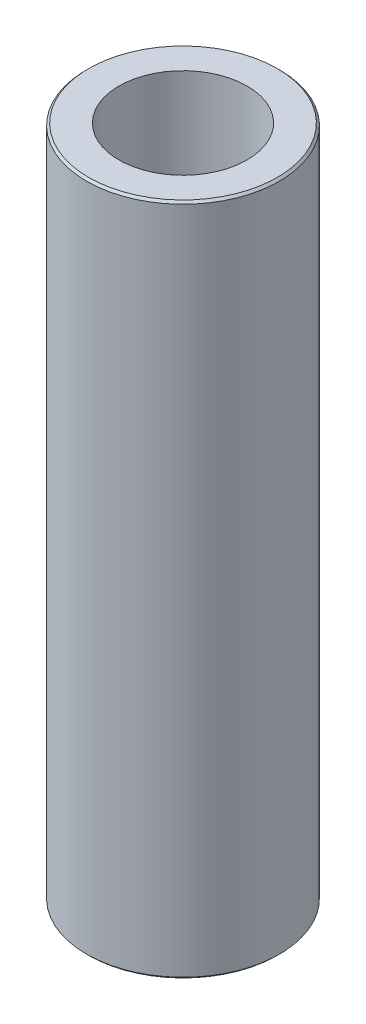
SolidWorks part; units mm, degrees
ref_plane "Front Plane" through (0, 0, 0) normal (0, 0, 1) x (1, 0, 0)
ref_plane "Top Plane" through (0, 0, 0) normal (0, 1, 0) x (1, 0, 0)
ref_plane "Right Plane" through (0, 0, 0) normal (1, 0, 0) x (0, 0, -1)
sketch "Sketch1" plane through (0, 0, 0) normal (0, 1, 0) x (1, 0, 0)
  circle A0 centre (0, 0) radius 45
  dimension "SHAFT_OD" = 90
extrude "Boss-Extrude1" add sketch "Sketch1" along normal blind 314.2264
sketch "Sketch2" plane through (0, 0, 0) normal (0, 1, 0) x (1, 0, 0)
  circle A0 centre (0, 0) radius 29.885
  dimension "BORE_D" = 59.7699
extrude "Cut-Extrude1" cut sketch "Sketch2" along normal through all
chamfer "Chamfer1" distance 1.0109 angle 45 2 edges at (0, 314.2264, 45) (0, 0, 45)
